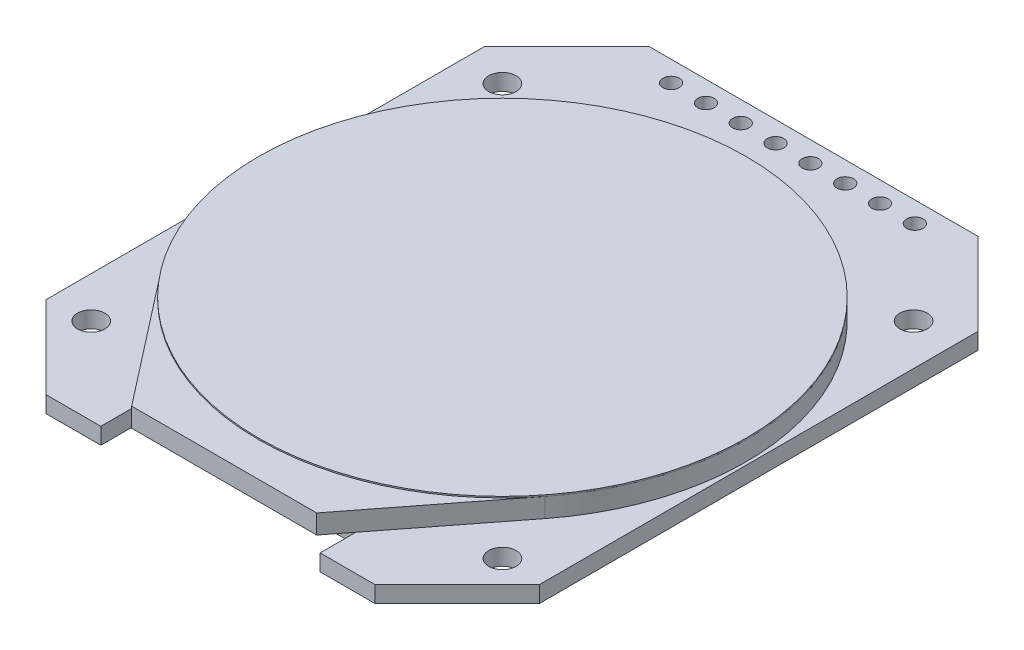
SolidWorks part; units mm, degrees
ref_plane "Front Plane" through (0, 0, 0) normal (0, 0, 1) x (1, 0, 0)
ref_plane "Top Plane" through (0, 0, 0) normal (0, 1, 0) x (1, 0, 0)
ref_plane "Right Plane" through (0, 0, 0) normal (1, 0, 0) x (0, 0, -1)
sketch "Sketch2" plane through (0, 0, 0) normal (0, 1, 0) x (1, 0, 0)
  line L0 (-18, -16) -> (-12, -22)
  line L1 (-18, -22) -> (18, -22)
  line L2 (-18, -22) -> (-18, 22)
  line L3 (-18, 22) -> (18, 22)
  line L4 (18, -22) -> (18, 22)
  line L5 (-18, -22) -> (18, 22) construction
  line L6 (-18, 22) -> (18, -22) construction
  line L7 (12, -22) -> (18, -16)
  line L8 (18, 16) -> (12, 22)
  line L9 (-12, 22) -> (-18, 16)
  line L10 (-8.89, 20.5) -> (-6.35, 20.5) construction
  line L11 (-6.35, 20.5) -> (-3.81, 20.5) construction
  line L12 (-3.81, 20.5) -> (-1.27, 20.5) construction
  line L13 (-1.27, 20.5) -> (1.27, 20.5) construction
  line L14 (0, 0) -> (0, 35.046) construction
  line L15 (-8, -22) -> (-8, -19)
  line L16 (-8, -19) -> (8, -19)
  line L17 (8, -19) -> (8, -22)
  line L18 (-14.0436, -11.6207) -> (-6.75, -21)
  line L19 (-6.75, -21) -> (6.75, -21)
  line L20 (6.75, -21) -> (14.0436, -11.6207)
  circle A0 centre (15, -15.7) radius 1
  circle A1 centre (-15, -15.7) radius 1
  circle A2 centre (-15, 14.3) radius 1
  circle A3 centre (15, 14.3) radius 1
  circle A4 centre (0, -0.7) radius 16.2
  circle A5 centre (0, -0.7) radius 17.79
  circle A6 centre (-1.27, 20.5) radius 0.6
  circle A7 centre (-3.81, 20.5) radius 0.6
  circle A8 centre (-6.35, 20.5) radius 0.6
  circle A9 centre (-8.89, 20.5) radius 0.6
  circle A10 centre (1.27, 20.5) radius 0.6
  circle A11 centre (3.81, 20.5) radius 0.6
  circle A12 centre (6.35, 20.5) radius 0.6
  circle A13 centre (8.89, 20.5) radius 0.6
  point P0 (0, 0)
  point P34 (0, 20.5)
  point P48 (0, -19)
  point P52 (0, -21)
  dimension "D7" = 2
  dimension "D12" = 32.4
  dimension "D13" = 6.5
  dimension "D14" = 35.58
  dimension "D16" = 1.2
  dimension "D1" = 6
  dimension "D2" = 6
  dimension "D3" = 6
  dimension "D4" = 6
  dimension "D5" = 36
  dimension "D6" = 44
  dimension "D8" = 6.3
  dimension "D9" = 3
  dimension "D10" = 3
  dimension "D11" = 7.7
  dimension "D15" = 2.54
  dimension "D17" = 1.5
  dimension "D18" = 41
  dimension "D19" = 16
  dimension "D20" = 13.5
  dimension "D21" = 1
extrude "Boss-Extrude1" add sketch "Sketch2" against normal blind 1.2 contours A5 L20 L17 L1 L7 L4 L8 L3 L9 L2 L0 L15 L18 A12 A10 A9 A8 A7 A6 A3 A2 A1 A0 A11 A13 | A5 A4 | A4 | A5 L18 L15 L16 L17 L20 region at (-17.9431, 0, 0) region at (-10.7917, 0, 15.3277) region at (-5.6094, 0, -15.6514) region at (0, 0, 0.7)
extrude "Boss-Extrude2" add sketch "Sketch2<3>" along normal blind 1.4 separate body contours A5 L18 L15 L16 L17 L20 | A5 A4 | L19 L20 L17 L16 L15 L18 | A4 region at (-10.7917, 0, 15.3277) region at (0, 0, 19.9689) region at (-5.6094, 0, -15.6514) region at (0, 0, 0.7)
sketch "Sketch2<3>" plane through (0, 0, 0) normal (0, 1, 0) x (1, 0, 0) same geometry as "Sketch2"
extrude "Boss-Extrude3" add sketch "Sketch2<4>" along normal blind 0.1 from surface separate body contours A5 A4 | A4 region at (-5.6094, 0, -15.6514) region at (0, 0, 0.7) starting at face at (0, 1.4, 9.1327)
sketch "Sketch2<4>" plane through (0, 0, 0) normal (0, 1, 0) x (1, 0, 0) same geometry as "Sketch2"
